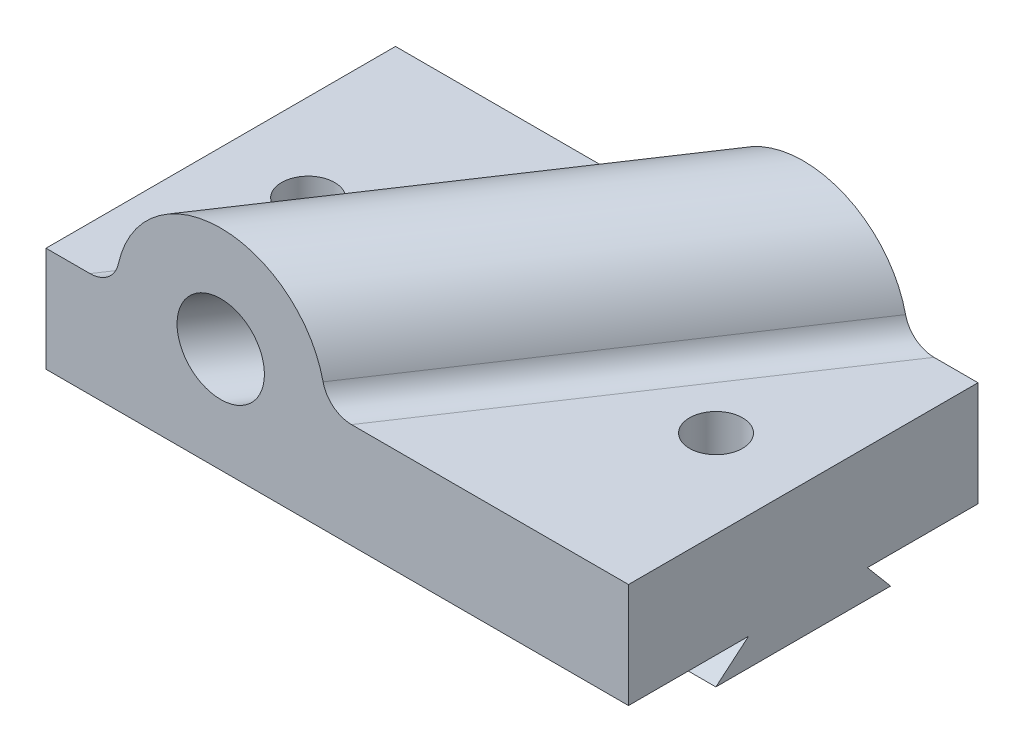
SolidWorks part; units mm, degrees
ref_plane "Front Plane" through (0, 0, 0) normal (0, 0, 1) x (1, 0, 0)
ref_plane "Top Plane" through (0, 0, 0) normal (0, 1, 0) x (1, 0, 0)
ref_plane "Right Plane" through (0, 0, 0) normal (1, 0, 0) x (0, 0, -1)
sketch "Sketch1" plane through (0, 0, 0) normal (1, 0, 0) x (0, 0, -1)
  line L0 (20.6081, 0) -> (15, -4.73)
  line L1 (0, 0) -> (60, 0)
  line L2 (0, 0) -> (0, 18)
  line L3 (0, 18) -> (60, 18)
  line L4 (60, 0) -> (60, 18)
  line L5 (15, -4.73) -> (45, -4.73)
  line L6 (45, -4.73) -> (41.0106, 0)
  line L7 (0, 0) -> (15, -4.73) construction
  line L8 (45, -4.73) -> (60, 0) construction
  dimension "D1" = 30
  dimension "D2" = 18
  dimension "D3" = 60
  dimension "D4" = 4.73
extrude "Boss-Extrude1" add sketch "Sketch1" along normal blind 100 contours L1 L4 L3 L2 | L5 L6 L1 L0 region at (0, -2.5151, -30.379) region at (0, 9, -30)
sketch "Sketch2" plane through (0, 0, 0) normal (0, 0, 1) x (1, 0, 0)
  line L0 (100, 18) -> (0, 18) construction
  line L1 (0, 18) -> (7.5501, 18)
  line L2 (22.5, 18) -> (37.5, 18)
  line L3 (52.4499, 18) -> (100, 18)
  line L4 (7.5501, 18) -> (52.4499, 18)
  circle A0 centre (30, 18) radius 7.5
  arc A1 (47.5695, 21.913) -> (12.4305, 21.913) centre (30, 18) ccw
  arc A2 (47.5695, 21.913) -> (52.4499, 18) centre (52.4499, 23) ccw
  arc A3 (12.4305, 21.913) -> (7.5501, 18) centre (7.5501, 23) cw
  point P14 (48, 18)
  dimension "D2" = 15
  dimension "D3" = 36
  dimension "D4" = 5
  dimension "D5" = 5
  dimension "D1" = 30
sketch "Sketch3" plane through (0, 0, 0) normal (0, 1, 0) x (1, 0, 0)
  line L0 (30, 0) -> (70, 60)
  line L1 (22.5, 0) -> (37.5, 0) construction
  line L2 (100, 60) -> (0, 60) construction
  dimension "D1" = 30
sketch "Sketch6" plane through (0, 0, -60) normal (0, 0, -1) x (-1, 0, 0)
  line L0 (-52.4499, 18) -> (-100, 18) construction
  circle A0 centre (-69.9965, 18) radius 7.5
  dimension "D1" = 15
  dimension "D2" = 30.0035
sweep "Sweep5" add profiles "Sketch2" path "Sketch3"
sweep "Cut-Sweep3" cut profiles "Sketch6" path "Sketch3<4>"
sketch "Sketch3<4>" plane through (0, 0, 0) normal (0, 1, 0) x (1, 0, 0) same geometry as "Sketch3"
sketch "Sketch7" plane through (0, 0, 0) normal (0, 1, 0) x (1, 0, 0)
  line L0 (49.9903, 60) -> (50.0097, 0) construction
  line L1 (52.4305, 60) -> (47.5501, 60) construction
  line L2 (47.5695, 0) -> (52.4499, 0) construction
  line L3 (0, 0) -> (0, 60) construction
  circle A0 centre (15, 30) radius 4.5517
  circle A1 centre (85, 30.0227) radius 4.5517
  point P10 (0, 30)
  dimension "D1" = 15
extrude "Cut-Extrude1" cut sketch "Sketch7" against normal through all both and the other way through all
